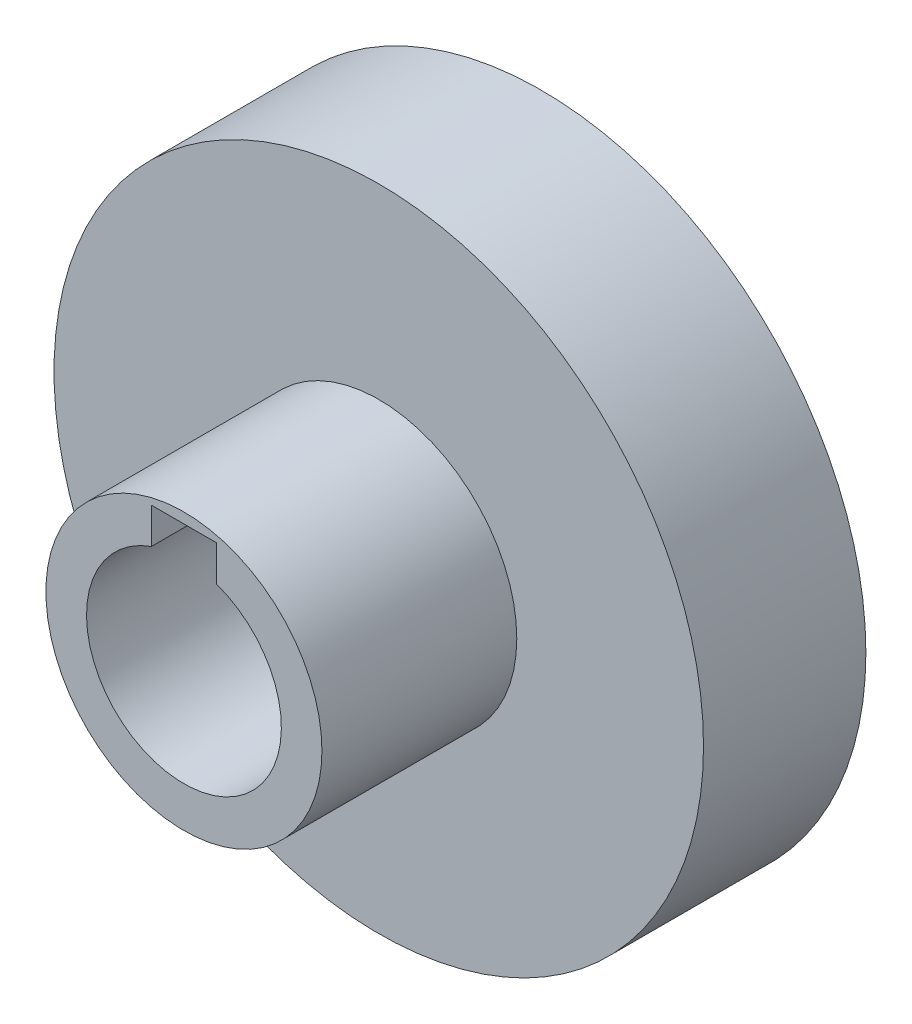
SolidWorks part; units mm, degrees
ref_plane "Front Plane" through (0, 0, 0) normal (1, 0, 0) x (0, 1, 0)
ref_plane "Top Plane" through (0, 0, 0) normal (0, 0, 1) x (0, 1, 0)
ref_plane "Right Plane" through (0, 0, 0) normal (0, 1, 0) x (-1, 0, 0)
sketch "Sketch1" plane through (0, 0, 0) normal (0, 0, 1) x (0, 1, 0)
  circle A0 centre (0, 0) radius 10
  dimension "D1" = 20
extrude "Boss-Extrude1" add sketch "Sketch1" along normal blind 5 contours A0
sketch "Sketch3" plane through (0, 0, 5) normal (0, 0, 1) x (1, 0, 0)
  circle A0 centre (0, 0) radius 4.25
  dimension "D1" = 8.5
extrude "Boss-Extrude2" add sketch "Sketch3" along normal blind 6
sketch "Sketch2" plane through (0, 0, 11) normal (0, 0, 1) x (1, 0, 0)
  line L1 (-1, 3.9284) -> (1, 3.9284)
  line L2 (-1, 3.9284) -> (-1, 2.8284)
  line L4 (1, 3.9284) -> (1, 2.8284)
  arc A0 (-1, 2.8284) -> (1, 2.8284) centre (0, 0) ccw
  dimension "D1" = 6
  dimension "D4" = 1.1
  dimension "D2" = 2
  dimension "D3" = 1.1
  dimension "D5" = 0
extrude "Cut-Extrude1" cut sketch "Sketch2" against normal up to surface (6 mm away) contours A0 L4 L1 L2 up to face at (4.25, 0, 5)
split "Split1" bodies to split 102 resulting bodies 104 105 split by face at (4.25, 0, 5)
